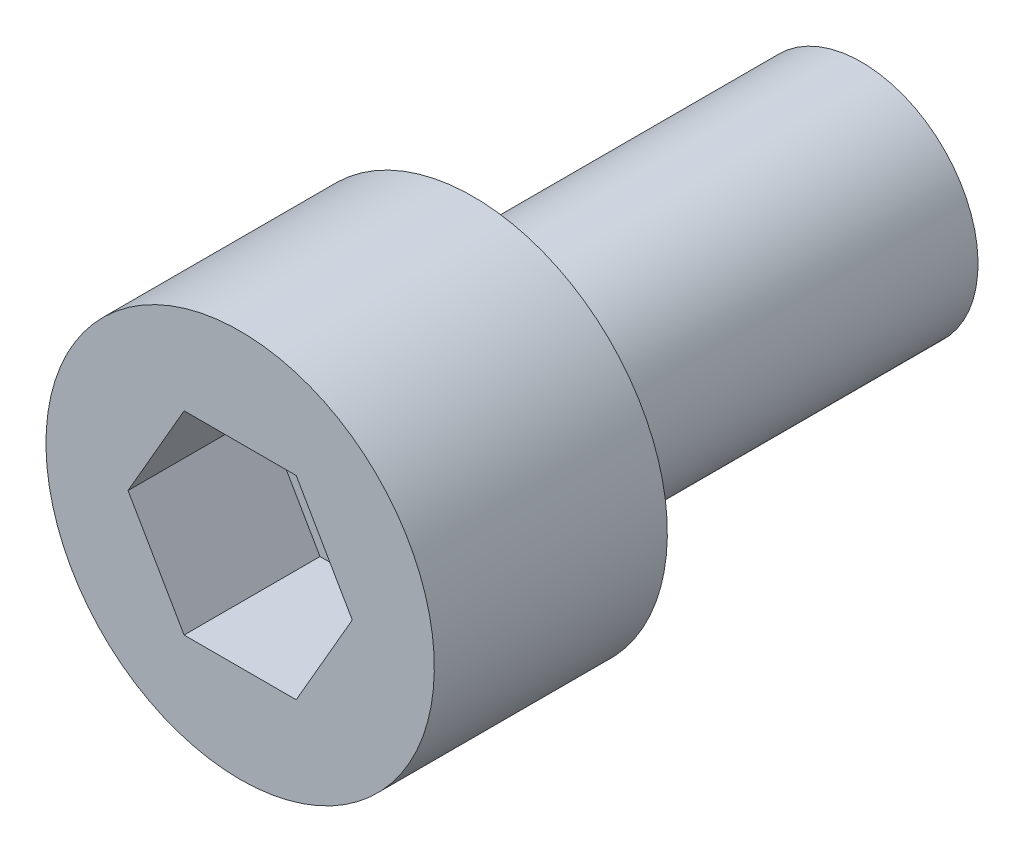
SolidWorks part; units mm, degrees
material "AISI 304"
ref_plane "Front Plane" through (0, 0, 0) normal (0, 0, 1) x (1, 0, 0)
ref_plane "Top Plane" through (0, 0, 0) normal (0, 1, 0) x (1, 0, 0)
ref_plane "Right Plane" through (0, 0, 0) normal (1, 0, 0) x (0, 0, -1)
ref_axis "Axis1" through (0, 0, -52.8182) along (0, 0, 1)
ref_axis "Axis2" through (0, -15.5981, 0) along (0, 1, 0)
ref_axis "Axis3" through (-12.2581, 0, 0) along (1, 0, 0)
sketch "Sketch1" plane through (0, 0, 0) normal (1, 0, 0) x (0, 0, -1)
  line L0 (-6, 0) -> (-6, 5)
  line L1 (-6, 5) -> (0, 5)
  line L2 (0, 5) -> (0, 3)
  line L3 (0, 3) -> (10, 3)
  line L4 (10, 3) -> (10, 0)
  line L5 (10, 0) -> (-6, 0)
  line L6 (-5.5849, 0) -> (13.8966, 0) construction
  dimension "D1" = 6
  dimension "D2" = 10
  dimension "D3" = 6
  dimension "Length" = 10
revolve "Revolve1" add sketch "Sketch1" angle 360 about L6
cosmetic thread "Cosmetic Thread1" parameters "D1"=10, "D2"=4.891
sketch "Sketch2" plane through (0, 0, 6) normal (0, 0, 1) x (1, 0, 0)
  line L1 (1.4434, -2.5) -> (2.8868, 0)
  line L2 (2.8868, 0) -> (1.4434, 2.5)
  line L3 (1.4434, 2.5) -> (-1.4434, 2.5)
  line L4 (-1.4434, 2.5) -> (-2.8868, 0)
  line L5 (-2.8868, 0) -> (-1.4434, -2.5)
  line L6 (-1.4434, -2.5) -> (1.4434, -2.5)
  circle A0 centre (0, 0) radius 2.5 construction
  dimension "D1" = 5
extrude "Cut-Extrude1" cut sketch "Sketch2" against normal blind 3.5
